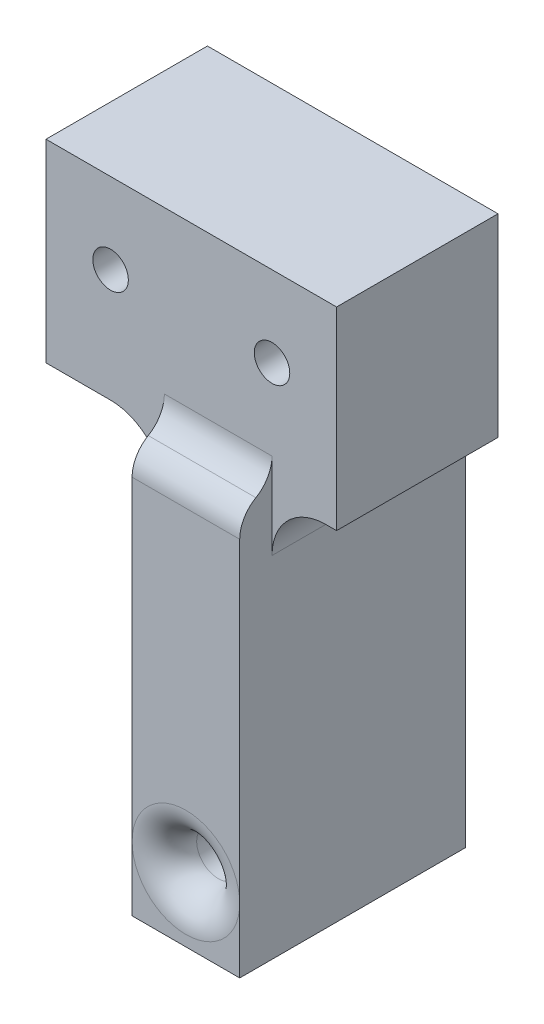
SolidWorks part; units mm, degrees
material "ABS"
ref_plane "前视基准面" through (0, 0, 0) normal (0, 0, 1) x (1, 0, 0)
ref_plane "上视基准面" through (0, 0, 0) normal (0, 1, 0) x (1, 0, 0)
ref_plane "右视基准面" through (0, 0, 0) normal (1, 0, 0) x (0, 0, -1)
other "Configuration Table"
sketch "草图2" plane through (0, 0, 0) normal (0, 0, 1) x (1, 0, 0)
  line L0 (-17.174, 0) -> (15.567, 0) construction
  line L1 (-13.5, -7.5) -> (13.5, -7.5) construction
  line L2 (-13.5, -7.5) -> (-13.5, 7.5)
  line L3 (-13.5, 7.5) -> (13.5, 7.5)
  line L4 (13.5, -7.5) -> (13.5, 7.5)
  line L5 (-13.5, -7.5) -> (13.5, 7.5) construction
  line L6 (-13.5, 7.5) -> (13.5, -7.5) construction
  line L7 (-13.5, -7.5) -> (-13.5, -10.5)
  line L8 (-13.5, -10.5) -> (13.5, -10.5)
  line L9 (13.5, -10.5) -> (13.5, -7.5)
  circle A0 centre (7.5, 0) radius 1.65
  circle A1 centre (-7.5, 0) radius 1.65
  point P0 (0, 0)
  dimension "D4" = 6
  dimension "D5" = 3.3
  dimension "D1" = 27
  dimension "D2" = 15
  dimension "D3" = 6
  dimension "D6" = 3
extrude "凸台-拉伸1" add sketch "草图2" along normal blind 15
sketch "草图4" plane through (0, -10.5, 0) normal (0, -1, 0) x (1, 0, 0)
  line L1 (-2.5, 18) -> (7.5, 18)
  line L2 (-2.5, 18) -> (-2.5, -3)
  line L3 (-2.5, -3) -> (7.5, -3)
  line L4 (7.5, 18) -> (7.5, -3)
  line L6 (-13.5, 15) -> (-13.5, 0) construction
  line L7 (-13.5, 15) -> (13.5, 15) construction
  line L8 (-13.5, 0) -> (13.5, 0) construction
  point P4 (2.5, -1.2718)
  point P5 (2.5, 15.8254)
  dimension "D1" = 10
  dimension "D2" = 11
  dimension "D3" = 3
  dimension "D4" = 3
extrude "凸台-拉伸2" add sketch "草图4" along normal blind 37.5
sketch "草图5" plane through (0, 0, 0) normal (0, 0, -1) x (-1, 0, 0)
  line L0 (-2.5, -43.4593) -> (-2.5, 12.043) construction
  line L1 (2.5, -48) -> (2.5, -10.5) construction
  line L2 (2.5, -48) -> (-7.5, -48) construction
  circle A0 centre (-2.5, -42) radius 2
  dimension "D2" = 4
  dimension "D3" = 6
  dimension "D1" = 5
extrude "切除-拉伸1" cut sketch "草图5" against normal through all and the other way through all
fillet "圆角1" radius 3 4 edges at (0.5, -42, 18) (2.5, -10.5, 0) (2.5, -10.5, 15) (0.5, -42, -3)
fillet "圆角2" radius 3 2 edges at (2.5, -10.5, -3) (2.5, -10.5, 18)
fillet "圆角3" radius 5 2 edges at (7.5, -10.5, 7.5) (-2.5, -10.5, 7.5)
